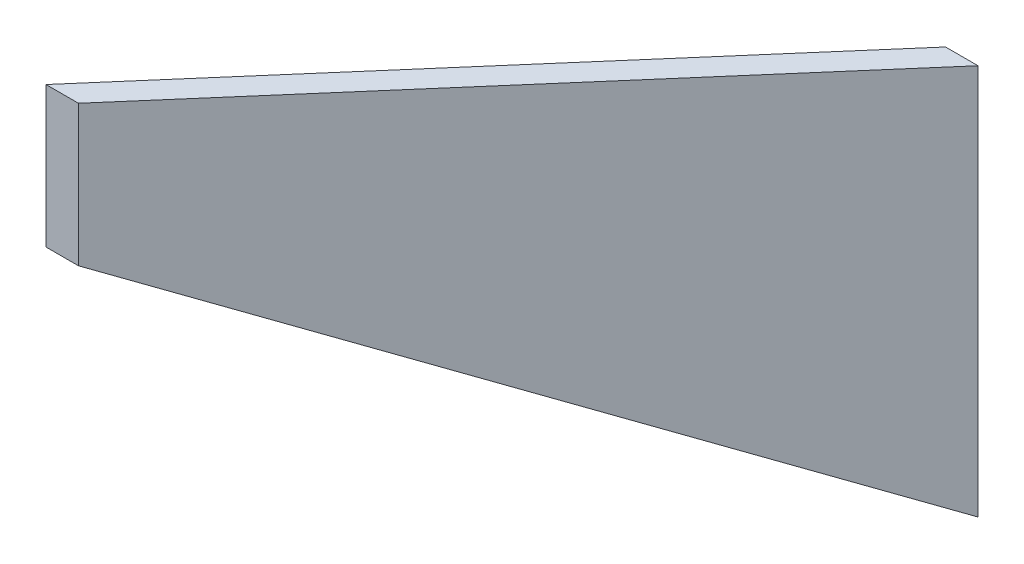
SolidWorks part; units mm, degrees
ref_plane "Front Plane" through (0, 0, 0) normal (0, 0, 1) x (1, 0, 0)
ref_plane "Top Plane" through (0, 0, 0) normal (0, 1, 0) x (1, 0, 0)
ref_plane "Right Plane" through (0, 0, 0) normal (1, 0, 0) x (0, 0, -1)
ref_plane "Plane3" through (0, 0, 127) normal (0, 0, 1) x (1, 0, 0)
ref_plane "Plane1" through (-63.5, 0, 0) normal (1, 0, 0) x (0, 0, -1)
ref_plane "Plane2" through (0, 149.86, 0) normal (0, 1, 0) x (1, 0, 0)
sketch "Sketch2" plane through (0, 0, 0) normal (0, 1, 0) x (1, 0, 0)
  line L0 (-57.15, 0) -> (224.536, 0)
  line L1 (224.536, 0) -> (-24.3577, -163.9616)
  line L2 (-24.3577, -163.9616) -> (-57.15, 0)
  line L3 (0, 0) -> (0, -127) construction
  line L4 (-31.75, -127) -> (31.75, -127) construction
  point P2 (0, 0)
  dimension "D1" = 281.686
  dimension "D2" = 57.15
  dimension "D3" = 63.5
  dimension "D4" = 127
extrude "Boss-Extrude1" add sketch "Sketch2" along normal blind 152.4
sketch "Sketch3" plane through (-63.5, 0, 0) normal (1, 0, 0) x (0, 0, -1)
  line L0 (0, 76.2) -> (-127, 76.2) construction
  line L1 (0, 152.4) -> (0, 0) construction
  line L2 (-127, 44.45) -> (-127, 107.95) construction
  line L3 (0, 152.4) -> (-127, 107.95)
  line L4 (0, 0) -> (-127, 44.45)
  line L5 (-127, 107.95) -> (-217.7143, 76.2)
  line L6 (-127, 44.45) -> (-217.7143, 76.2)
  line L7 (0, 152.4) -> (0, 0)
  point P7 (-127, 76.2)
  dimension "D1" = 127
  dimension "D2" = 63.5
extrude "Cut-Extrude2" cut sketch "Sketch3" along normal through all flip side to cut
shell "Shell1" thickness 6.35 removed face at (83.693, 76.2, 0)
sketch "Sketch8" plane through (0, 0, 127) normal (0, 0, 1) x (1, 0, 0)
  line L1 (-92.1964, -50.8668) -> (173.8662, -50.8668)
  line L2 (-92.1964, -50.8668) -> (-92.1964, 231.3249)
  line L3 (-92.1964, 231.3249) -> (173.8662, 231.3249)
  line L4 (173.8662, -50.8668) -> (173.8662, 231.3249)
extrude "Cut-Extrude6" cut sketch "Sketch8" along normal through all
sketch "Sketch4" plane through (-63.5, 0, 0) normal (1, 0, 0) x (0, 0, -1)
  line L1 (0, 152.4) -> (0, 145.6723)
  line L2 (0, 145.6723) -> (-163.9616, 88.2857)
  line L4 (-163.9616, 64.1143) -> (0, 6.7277)
  line L5 (0, 152.4) -> (-163.9616, 95.0134)
  line L7 (-163.9616, 57.3866) -> (0, 0)
  line L8 (-163.9616, 95.0134) -> (-163.9616, 57.3866) construction
  line L9 (-163.9616, 95.0134) -> (-163.9616, 88.2857)
  line L10 (-163.9616, 64.1143) -> (-163.9616, 57.3866)
  line L11 (0, 152.4) -> (0, 0) construction
  line L12 (0, 0) -> (0, 6.7277)
  line L13 (-127, 107.95) -> (0, 152.4) construction
  line L14 (-127, 44.45) -> (0, 0) construction
extrude "Cut-Extrude3" cut sketch "Sketch4" along normal through all
sketch "Sketch5" plane through (0, 149.86, 0) normal (0, 1, 0) x (1, 0, 0)
  line L0 (-20.1978, -152.3824) -> (-18.6358, -160.1922)
  line L1 (31.75, -127) -> (224.536, 0) construction
  line L2 (-25.2742, -127) -> (-50.6742, 0) construction
  line L3 (-18.6358, -160.1922) -> (344.3171, -160.1922)
  line L4 (344.3171, -160.1922) -> (317.8797, 72.8643)
  line L5 (317.8797, 72.8643) -> (-35.1367, 43.3166)
  line L6 (-35.1367, 43.3166) -> (-20.1978, -152.3824)
extrude "Cut-Extrude4" cut sketch "Sketch5" against normal through all flip side to cut
ref_plane "Plane4" through (156.5838, 0, -103.1514) normal (-0.8351, 0, 0.5501) x (0, -1, 0)
